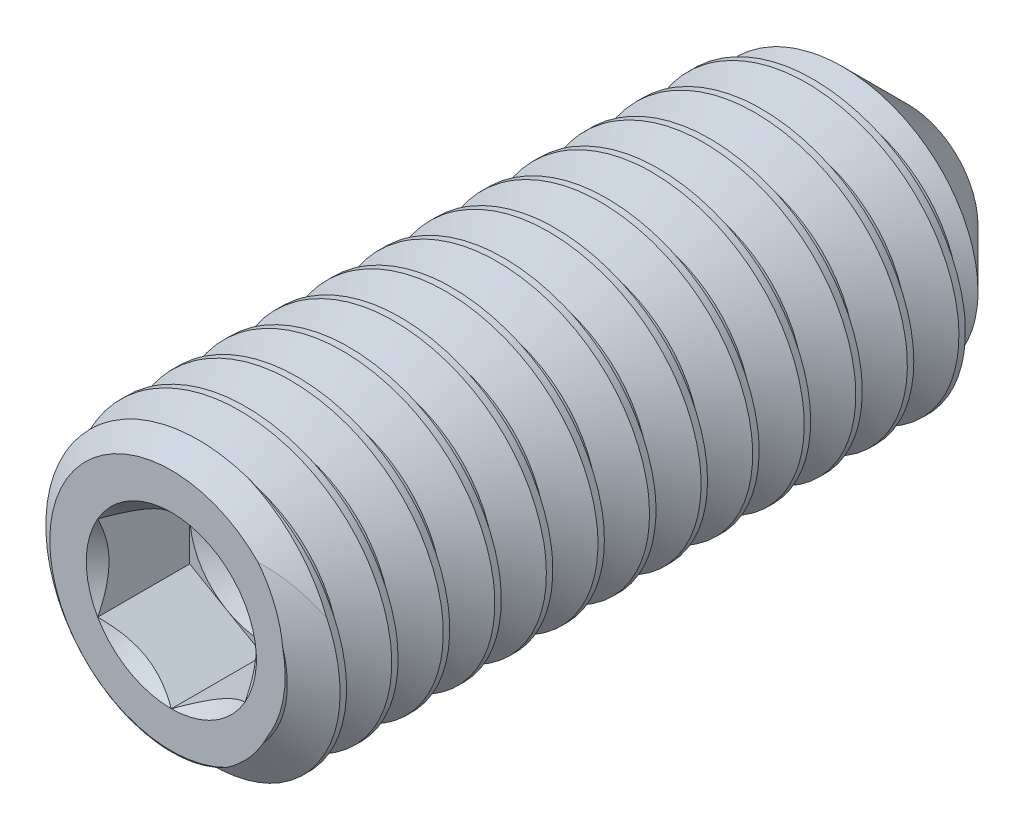
SolidWorks part; units mm, degrees
other "Imported1" parameters "D3"=11, "D1"=46.842, "Length"=10, "Drive Size"=2, "Thread Size"=4, "Thread Pitch"=0.7, "hex Depth"=1.25, "D2"=0.9112, "Dia"=12, "D4"=2.3829, "Cup Point Dia"=3.3528, "D5"=1.436, "D6"=1.4986, "D7"=5.0014, "Pitch"=1.75
ref_plane "Front" through (0, 0, 0) normal (0, 0, 1) x (1, 0, 0)
ref_plane "Top" through (0, 0, 0) normal (0, 1, 0) x (1, 0, 0)
ref_plane "Right" through (0, 0, 0) normal (1, 0, 0) x (0, 0, -1)
sketch "Sketch1" plane through (0, 0, 0) normal (1, 0, 0) x (0, 0, -1)
  line L0 (5, 2) -> (-5, 2) construction
  line L1 (-5, 2) -> (-5, -2) construction
  line L2 (-5, -2) -> (5, -2) construction
  line L3 (5, -2) -> (5, 2) construction
  line L4 (-5, 1) -> (-5, -1) construction
  line L5 (4.9562, 2.0758) -> (5.6562, 2.0758) construction
  line L6 (5.6562, 2.0758) -> (5.3062, 1.4696) construction
  line L7 (5.3062, 1.4696) -> (4.9562, 2.0758) construction
  line L8 (4.9781, 2.0379) -> (5.6344, 2.0379) construction
  line L9 (5, 2) -> (5.6125, 2) construction
  line L10 (5.3063, 2.0758) -> (5.3063, 2) construction
  line L11 (5.2625, 1.5453) -> (5.35, 1.5453) construction
  line L12 (5.3063, 1.5453) -> (5.3062, 1.4696) construction
  point P3 (0, 2)
  point P19 (5.3063, 2.0379)
  point P24 (-5, 0)
  point P25 (-5, 0)
  dimension "D1" = 0.0875
sketch "Sketch11" plane through (0, 0, 0) normal (1, 0, 0) x (0, 0, -1)
  line L0 (-5, 0) -> (-5, 1.65)
  line L1 (-5, 1.65) -> (-4.7549, 2)
  line L2 (-4.7549, 2) -> (3.95, 2)
  line L3 (3.95, 2) -> (5, 0.95)
  line L4 (5, 0.95) -> (4.4292, 0)
  line L5 (4.4292, 0) -> (-5, 0)
  line L6 (4.4292, 0) -> (5, 0) construction
  line L7 (5, 0) -> (5, 0.95) construction
  line L8 (5, -0.95) -> (4.4292, 0) construction
  line L9 (-4.7549, -2) -> (3.95, -2) construction
  line L10 (-5, -2) -> (5, -2) construction
  line L11 (-5, 2) -> (-5, -2) construction
  line L12 (5, -2) -> (5, 2) construction
  point P11 (2.55, -2)
  point P12 (-5, 2)
  dimension "D3" = 35
  dimension "D5" = 118
  dimension "D6" = 45
  dimension "D1" = 0.35
  dimension "D2" = 2.45
  dimension "D4" = 1.05
revolve "Revolve1" add sketch "Sketch11" angle 360 about L6
sketch "Sketch2" plane through (0, 0, 5) normal (0, 0, 1) x (1, 0, 0)
  line L1 (0, 1.1547) -> (-1, 0.5774)
  line L2 (-1, 0.5774) -> (-1, -0.5774)
  line L3 (-1, -0.5774) -> (0, -1.1547)
  line L4 (0, -1.1547) -> (1, -0.5774)
  line L5 (1, -0.5774) -> (1, 0.5774)
  line L6 (1, 0.5774) -> (0, 1.1547)
  circle A0 centre (0, 0) radius 1 construction
  circle A1 centre (0, 0) radius 2 construction
extrude "Cut-Extrude1" cut sketch "Sketch2" against normal blind 1.25
sketch "Sketch3" plane through (0, 0, 5) normal (0, 0, 1) x (1, 0, 0)
  circle A0 centre (0, 0) radius 1.1547
extrude "Cut-Extrude2" cut sketch "Sketch3" against normal through all draft 45
sketch "Sketch4" plane through (0, 0, 3.75) normal (0, 0, 1) x (1, 0, 0)
  circle A0 centre (0, 0) radius 1 construction
  circle A1 centre (0, 0) radius 1
extrude "Cut-Extrude3" cut sketch "Sketch4" against normal through all draft 60
sketch "Sketch13" plane through (0, 0, 0) normal (1, 0, 0) x (0, 0, -1)
  line L0 (0, -2) -> (0, 2) construction
  line L2 (-4.7549, 2) -> (3.95, 2) construction
  line L4 (4.4292, 0) -> (-5, 0) construction
  point P0 (0.4292, 0)
  point P4 (0, 0)
  point P9 (-0.4292, 0)
  dimension "D1" = 4
ref_plane "Plane1" through (0, 0, -5) normal (0, 0, 1) x (1, 0, 0)
sketch "Sketch5" plane through (0, 0, -5) normal (0, 0, 1) x (1, 0, 0)
  circle A0 centre (0, 0) radius 2 construction
  circle A1 centre (0, 0) radius 2
curve "Helix/Spiral1" pitch 0.7 height 11 radius 2 centre (0, 0, -5) axis (0, 0, 1) start towards (0, 1, 0)
sketch "Sketch6" plane through (0, 0, 0) normal (1, 0, 0) x (0, 0, -1)
  line L0 (4.9562, 2.0758) -> (5.6562, 2.0758) construction
  line L1 (5.6562, 2.0758) -> (5.3062, 1.4696) construction
  line L2 (5.3062, 1.4696) -> (4.9562, 2.0758) construction
  line L3 (5.3062, 2.0758) -> (5.3062, 2) construction
  line L4 (5, 2) -> (5.6125, 2) construction
  line L5 (5.3062, 1.5453) -> (5.3062, 1.4696) construction
  line L6 (5.2625, 1.5453) -> (4.9781, 2.0379)
  line L7 (4.9781, 2.0379) -> (5.6344, 2.0379)
  line L8 (4.9781, 2.0379) -> (5.6344, 2.0379) construction
  line L10 (5.2625, 1.5453) -> (5.35, 1.5453) construction
  line L12 (5.35, 1.5453) -> (5.2625, 1.5453)
  line L13 (5.6344, 2.0379) -> (5.35, 1.5453)
  point P9 (5.3062, 2)
  point P14 (5.3062, 2.0379)
  point P15 (5.3062, 2.0379)
  point P16 (5.3062, 1.5453)
  dimension "D1" = 0.7
  dimension "D2" = 0.0875
sweep "Cut-Sweep1" cut profiles "Sketch6" path "Helix/Spiral1"
equation "\"D3@Helix/Spiral1\" = \"Length@Sketch1\" * 1.1"
equation "\"hex Depth@Cut-Extrude1\" = \"Drive Size@Sketch1\" * .625"
equation "\"D1@Sketch6\" = \"Thread Pitch@Sketch1\""
equation "\"D2@Sketch6\" = \"D1@Sketch6\" / 8"
equation "\"D1@Sketch11\" = \"Thread Pitch@Sketch1\" * .5"
equation "\"D2@Sketch11\" = \"Thread Pitch@Sketch1\" * 3.5"
equation "\"D1@Helix/Spiral1\" = \"Thread Pitch@Sketch1\""
equation "\"D4@Sketch11\" = \"Thread Pitch@Sketch1\" * 1.5"
equation "\"D1@Sketch1\" = \"Thread Pitch@Sketch1\" / 8"
equation "\"D1@Sketch13\"=\"Thread Size@Sketch1\""
